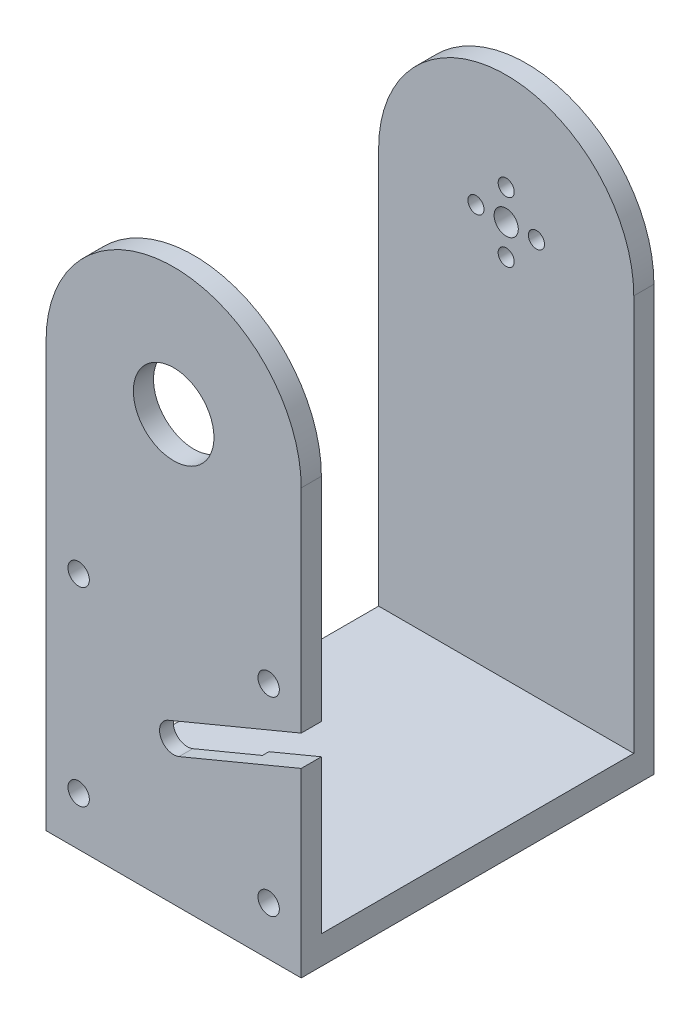
SolidWorks part; units mm, degrees
ref_plane "Front Plane" through (0, 0, 0) normal (0, 0, 1) x (1, 0, 0)
ref_plane "Top Plane" through (0, 0, 0) normal (0, 1, 0) x (1, 0, 0)
ref_plane "Right Plane" through (0, 0, 0) normal (1, 0, 0) x (0, 0, -1)
sketch "Sketch1" plane through (0, 0, 0) normal (0, 1, 0) x (1, 0, 0)
  line L0 (1.4078, 0) -> (58.7078, 0)
  line L1 (58.7078, 0) -> (61.7078, 0)
  line L2 (1.4078, 0) -> (-1.5922, 0)
  line L3 (-1.5922, 0) -> (-1.5922, 77.5)
  line L4 (-1.5922, 77.5) -> (61.7078, 77.5)
  line L5 (61.7078, 77.5) -> (61.7078, 0)
  line L6 (-1.5922, 77.5) -> (-1.5922, 82.5)
  line L7 (-1.5922, 82.5) -> (61.7078, 82.5)
  line L8 (61.7078, 82.5) -> (61.7078, 77.5)
  line L9 (-1.5922, 0) -> (-1.5922, -5)
  line L10 (-1.5922, -5) -> (61.7078, -5)
  line L11 (61.7078, -5) -> (61.7078, 0)
  line L12 (61.7078, 82.5) -> (86.7078, 82.5)
  line L13 (86.7078, 82.5) -> (86.7078, -5)
  line L14 (86.7078, -5) -> (61.7078, -5)
  line L15 (-1.5922, 82.5) -> (-26.5922, 82.5)
  line L16 (-26.5922, 82.5) -> (-26.5922, -5)
  line L17 (-26.5922, -5) -> (-1.5922, -5)
  dimension "D1" = 57.3
  dimension "D2" = 3
  dimension "D3" = 3
  dimension "D4" = 77.5
  dimension "D5" = 5
  dimension "D6" = 5
  dimension "D7" = 25
  dimension "D8" = 25
extrude "Boss-Extrude1" add sketch "Sketch1" against normal blind 7 contours L15 L16 L17 L10 L14 L13 L12 L7
extrude "Boss-Extrude2" add sketch "Sketch1<3>" along normal blind 60.3 contours L2 L9 L10 L11 L1 L0
sketch "Sketch1<3>" plane through (0, 0, 0) normal (0, 1, 0) x (1, 0, 0) same geometry as "Sketch1"
extrude "Boss-Extrude3" add sketch "Sketch1<5>" along normal blind 60.3 contours L4 L8 L7 L6
sketch "Sketch1<5>" plane through (0, 0, 0) normal (0, 1, 0) x (1, 0, 0) same geometry as "Sketch1"
sketch "Sketch2" plane through (0, 0, 0) normal (0, 0, -1) x (-1, 0, 0)
  line L0 (-30.0578, 60.3) -> (-30.0578, 0)
  line L1 (1.5922, 60.3) -> (-61.7078, 60.3) construction
  line L2 (1.5922, 0) -> (-61.7078, 0) construction
  line L3 (-30.0578, 0) -> (-30.0578, 28.65)
  line L5 (-53.6278, 52.22) -> (-6.4878, 52.22)
  line L6 (-53.6278, 52.22) -> (-53.6278, 5.08)
  line L7 (-53.6278, 5.08) -> (-6.4878, 5.08)
  line L8 (-6.4878, 52.22) -> (-6.4878, 5.08)
  line L9 (-53.6278, 52.22) -> (-6.4878, 5.08) construction
  line L10 (-53.6278, 5.08) -> (-6.4878, 52.22) construction
  circle A0 centre (-6.4878, 52.22) radius 2.65
  circle A1 centre (-53.6278, 52.22) radius 2.65
  circle A2 centre (-53.6278, 5.08) radius 2.65
  circle A3 centre (-6.4878, 5.08) radius 2.65
  circle A4 centre (-30.0578, 28.65) radius 3.5
  circle A5 centre (-30.0578, 28.65) radius 19.05
  dimension "D3" = 5.3
  dimension "D4" = 5.3
  dimension "D5" = 5.3
  dimension "D6" = 5.3
  dimension "D7" = 7
  dimension "D8" = 38.1
  dimension "D1" = 28.65
  dimension "D2" = 47.14
extrude "Cut-Extrude1" cut sketch "Sketch2" against normal up to surface (5 mm away) contours A3 | A2 | A4 | A1 | A0 up to face at (30.0578, 13.325, 5)
extrude "Cut-Extrude2" cut sketch "Sketch2<3>" against normal blind 1.6 contours A5
sketch "Sketch2<3>" plane through (0, 0, 0) normal (0, 0, -1) x (-1, 0, 0) same geometry as "Sketch2"
sketch "Sketch4" plane through (0, 0, 5) normal (0, 0, 1) x (1, 0, 0)
  line L0 (28.7132, 31.8814) -> (61.7078, 45.6115)
  line L1 (61.7078, 60.3) -> (61.7078, 0) construction
  line L2 (28.7132, 31.8814) -> (31.4025, 25.4186)
  line L3 (31.4025, 25.4186) -> (61.7078, 38.0296)
  line L4 (61.7078, 38.0296) -> (61.7078, 45.6115)
  circle A0 centre (30.0578, 28.65) radius 3.5 construction
extrude "Cut-Extrude3" cut sketch "Sketch4" against normal up to surface (5 mm away) up to face at (11.0078, 28.65, 0)
sketch "Sketch5" plane through (0, 0, 5) normal (0, 0, 1) x (1, 0, 0)
  line L0 (-1.5922, 0) -> (-21.5922, 0)
  line L1 (-1.5922, 0) -> (-1.5922, 20)
  line L2 (-1.5922, 60.3) -> (-1.5922, 0) construction
  line L3 (-1.5922, 20) -> (-21.5922, 0)
  line L4 (61.7078, 0) -> (61.7078, 20)
  line L5 (61.7078, 38.0296) -> (61.7078, 0) construction
  line L6 (61.7078, 0) -> (81.7078, 0)
  line L7 (81.7078, 0) -> (61.7078, 20)
  dimension "D1" = 20
  dimension "D2" = 20
  dimension "D3" = 20
  dimension "D4" = 20
sketch "Sketch6" plane through (0, 0, -82.5) normal (0, 0, -1) x (-1, 0, 0)
  line L0 (-61.7078, 0) -> (-81.7078, 0)
  line L1 (-61.7078, 0) -> (-61.7078, 20)
  line L2 (-61.7078, 60.3) -> (-61.7078, 0) construction
  line L3 (-61.7078, 20) -> (-81.7078, 0)
  line L4 (1.5922, 0) -> (21.5922, 0)
  line L5 (1.5922, 0) -> (26.5922, 0) construction
  line L6 (1.5922, 0) -> (1.5922, 20)
  line L7 (1.5922, 20) -> (21.5922, 0)
  dimension "D1" = 20
  dimension "D2" = 20
  dimension "D3" = 20
  dimension "D4" = 20
sketch "Sketch7" plane through (0, 0, -82.5) normal (0, 0, -1) x (-1, 0, 0)
  line L0 (-61.7078, 60.3) -> (-61.7078, 98.3)
  line L1 (1.5922, 60.3) -> (1.5922, 98.3)
  line L2 (1.5922, 98.3) -> (-61.7078, 98.3)
  line L3 (1.5922, 60.3) -> (-61.7078, 60.3)
  line L4 (-61.7078, 98.3) -> (1.5922, 98.3)
  arc A0 (1.5922, 98.3) -> (-61.7078, 98.3) centre (-30.0578, 98.3) ccw
  dimension "D1" = 38
  dimension "D2" = 38
  dimension "D3" = 63.3
extrude "Boss-Extrude6" add sketch "Sketch7" against normal blind 5 contours L0 A0 L1 L3
sketch "Sketch8" plane through (0, 0, 5) normal (0, 0, 1) x (1, 0, 0)
  line L0 (-1.5922, 60.3) -> (-1.5922, 98.3)
  line L1 (61.7078, 60.3) -> (61.7078, 98.3)
  line L2 (61.7078, 98.3) -> (-1.5922, 98.3)
  line L3 (-1.5922, 60.3) -> (61.7078, 60.3)
  arc A0 (61.7078, 98.3) -> (-1.5922, 98.3) centre (30.0578, 98.3) ccw
  dimension "D1" = 38
  dimension "D2" = 38
extrude "Boss-Extrude10" add sketch "Sketch8" against normal blind 5 contours L0 A0 L1 L3
sketch "Sketch15" plane through (0, 0, -82.5) normal (0, 0, -1) x (-1, 0, 0)
  circle A0 centre (-30.0578, 98.3) radius 3
  circle A1 centre (-30.0578, 98.3) radius 7.5
  circle A2 centre (-30.0578, 105.8) radius 2
  circle A3 centre (-22.5578, 98.3) radius 2
  circle A4 centre (-30.0578, 90.8) radius 2
  circle A5 centre (-37.5578, 98.3) radius 2
  dimension "D1" = 6
  dimension "D2" = 15
  dimension "D3" = 4
  dimension "D4" = 4
  dimension "D5" = 4
  dimension "D6" = 4
extrude "Cut-Extrude7" cut sketch "Sketch15" against normal up to surface (5 mm away) contours A4 | A5 | A2 | A0 | A3 up to face at (30.0578, 57.0625, -77.5)
sketch "Sketch16" plane through (0, 0, 5) normal (0, 0, 1) x (1, 0, 0)
  circle A0 centre (30.0578, 98.3) radius 10
  dimension "D1" = 20
extrude "Cut-Extrude8" cut sketch "Sketch16" against normal up to surface (5 mm away) up to face at (37.9329, 46.1333, 0)
sketch "Sketch17" plane through (0, -7, 0) normal (0, -1, 0) x (1, 0, 0)
  line L0 (30.0578, 5) -> (30.0578, -82.5)
  line L1 (86.7078, 5) -> (-26.5922, 5) construction
  line L2 (-26.5922, -82.5) -> (86.7078, -82.5) construction
  circle A0 centre (30.0578, -38.75) radius 30
  dimension "D2" = 60
  dimension "D1" = 87.5
sketch "Sketch20" plane through (0, 0, -82.5) normal (0, 0, -1) x (-1, 0, 0)
  line L0 (-61.7078, 0) -> (-76.7078, 0)
  line L1 (-86.7078, 0) -> (-61.7078, 0) construction
  line L2 (-76.7078, 0) -> (-61.7078, 98.3)
  line L3 (-61.7078, 98.3) -> (-61.7078, 0)
  line L4 (1.5922, 0) -> (16.5922, 0)
  line L5 (1.5922, 0) -> (26.5922, 0) construction
  line L6 (16.5922, 0) -> (1.5922, 98.3)
  line L7 (1.5922, 98.3) -> (1.5922, 0)
  dimension "D1" = 15
  dimension "D2" = 15
sketch "Sketch21" plane through (0, 0, 5) normal (0, 0, 1) x (1, 0, 0)
  line L0 (-1.5922, 0) -> (-16.5922, 0)
  line L1 (-26.5922, 0) -> (-1.5922, 0) construction
  line L2 (-16.5922, 0) -> (-1.5922, 98.3)
  line L3 (-1.5922, 98.3) -> (-1.5922, 0)
  line L4 (61.7078, 0) -> (76.7078, 0)
  line L5 (61.7078, 0) -> (86.7078, 0) construction
  line L6 (76.7078, 0) -> (61.7078, 98.3)
  line L7 (61.7078, 98.3) -> (61.7078, 0)
  dimension "D1" = 15
  dimension "D2" = 15
sketch "Sketch27" plane through (0, 0, 0) normal (0, 1, 0) x (1, 0, 0)
  line L0 (61.7078, 82.5) -> (86.7078, 82.5)
  line L1 (86.7078, 82.5) -> (86.7078, -5)
  line L2 (86.7078, -5) -> (61.7078, -5)
  line L3 (61.7078, -5) -> (61.7078, 82.5)
  line L4 (-1.5922, 82.5) -> (-26.5922, 82.5)
  line L5 (-26.5922, 82.5) -> (-26.5922, -5)
  line L6 (-26.5922, -5) -> (-1.5922, -5)
  line L7 (-1.5922, 0) -> (-1.5922, -5) construction
  line L8 (-26.5922, -5) -> (-1.5922, -5) construction
  line L9 (-1.5922, -5) -> (-1.5922, 82.5)
extrude "Cut-Extrude10" cut sketch "Sketch27" against normal up to surface (7 mm away) up to face at (30.0578, -7, -38.75)
sketch "Sketch31" plane through (0, 0, 0) normal (0, 1, 0) x (1, 0, 0)
  line L0 (61.7078, 0) -> (61.7078, 77.5)
  line L1 (61.7078, 38.75) -> (-1.1826, 38.75)
sketch "Sketch32" plane through (61.7078, 0, 0) normal (1, 0, 0) x (0, 0, -1)
  line L0 (82.5, 60.3) -> (77.5, 60.3)
  line L1 (82.5, 60.3) -> (82.5, 98.3) construction
  line L2 (82.5, 60.3) -> (82.5, 98.3) construction
  line L3 (77.5, 98.3) -> (77.5, 0) construction
sketch "Sketch33" plane through (0, 0, -77.5) normal (0, 0, 1) x (1, 0, 0)
  line L0 (61.7078, 60.3) -> (61.7078, 0)
  line L1 (61.7078, 30.15) -> (-1.5922, 30.15)
  line L2 (-1.5922, 98.3) -> (-1.5922, 0) construction
  circle A0 centre (30.0578, 30.15) radius 3.5
  dimension "D1" = 7
extrude "Boss-Extrude18" add sketch "Sketch33" against normal blind 20 contours A0
